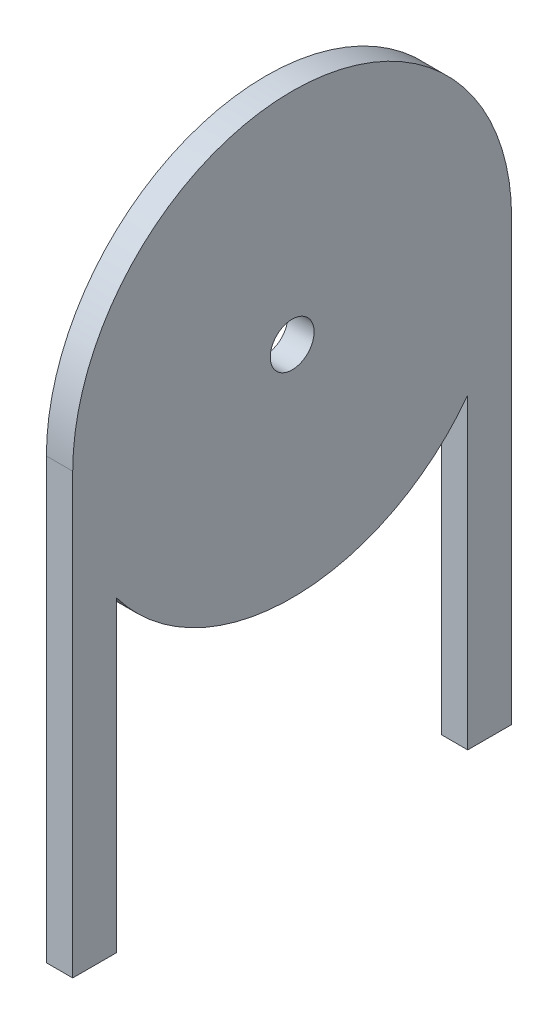
SolidWorks part; units mm, degrees
ref_plane "Front Plane" through (0, 0, 0) normal (0, 0, 1) x (1, 0, 0)
ref_plane "Top Plane" through (0, 0, 0) normal (0, 1, 0) x (1, 0, 0)
ref_plane "Right Plane" through (0, 0, 0) normal (1, 0, 0) x (0, 0, -1)
sketch "Sketch1" plane through (0, 0, 0) normal (1, 0, 0) x (0, 0, -1)
  line L0 (-25, 0) -> (-25, -50)
  line L1 (25, 0) -> (25, -50)
  line L2 (-20, -15) -> (-20, -50)
  line L3 (20, -15) -> (20, -50)
  line L4 (-25, -50) -> (-20, -50)
  line L5 (20, -50) -> (25, -50)
  arc A0 (-25, 0) -> (25, 0) centre (0, 0) cw
  circle A1 centre (0, 0) radius 2.5
  circle A2 centre (0, 0) radius 25
  dimension "D1" = 25
  dimension "D3" = 5
  dimension "D2" = 50
  dimension "D4" = 5
extrude "Boss-Extrude1" add sketch "Sketch1" along normal blind 3 contours A2 L0 L4 L2 | A0 A2 A1 | A2 L3 L5 L1 region at (0, -29.9555, 22.6238) region at (0, 24.2929, 0) region at (0, -29.9555, -22.6238)
